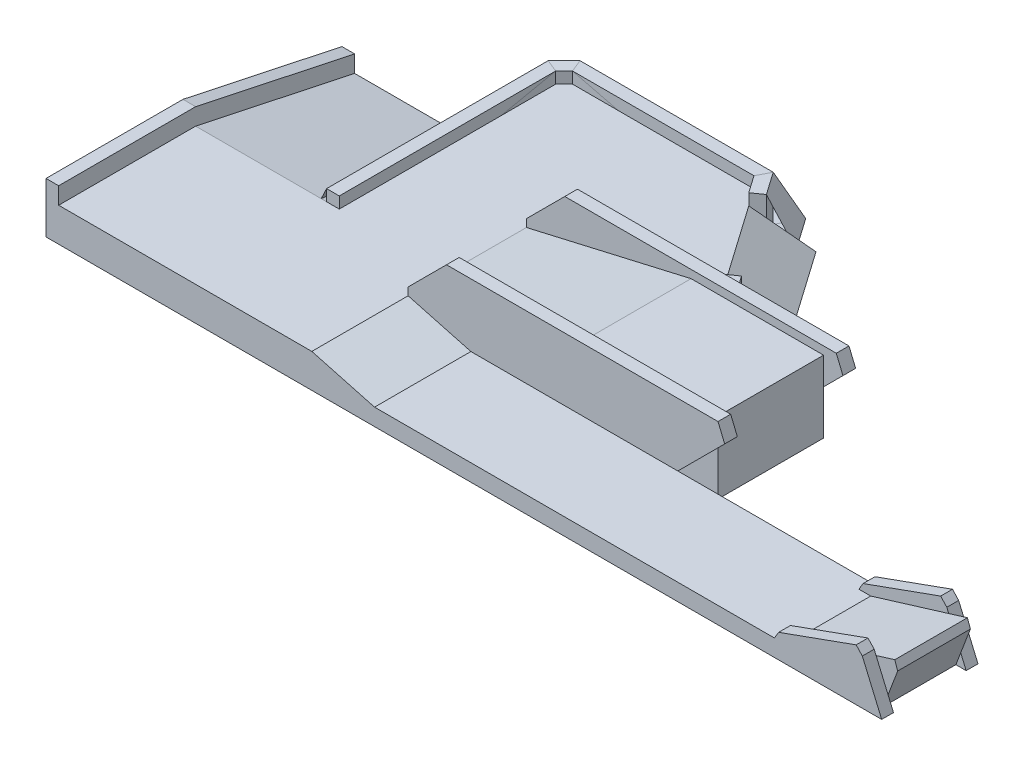
SolidWorks part; units mm, degrees
note: The reader was unsure of these and kept them because the rebuilt part matched: shared geometry of "草图13<4>", "草图18<2>", "草图18<3>", "草图19<2>".
ref_plane "前视基准面" through (0, 0, 0) normal (0, 0, 1) x (1, 0, 0)
ref_plane "上视基准面" through (0, 0, 0) normal (0, 1, 0) x (1, 0, 0)
ref_plane "右视基准面" through (0, 0, 0) normal (1, 0, 0) x (0, 0, -1)
sketch "草图1" plane through (0, 0, 0) normal (0, 1, 0) x (1, 0, 0)
  line L1 (-1498, -810.5) -> (1498, -810.5)
  line L2 (-1498, -810.5) -> (-1498, 810.5)
  line L3 (-1498, 810.5) -> (202, 810.5)
  line L5 (-1498, -810.5) -> (1498, 810.5) construction
  line L6 (-1498, 810.5) -> (1498, -810.5) construction
  line L8 (1498, -810.5) -> (1498, 1879.5)
  line L9 (2449, 3471.5) -> (202, 3471.5)
  line L11 (2449, 3471.5) -> (3563.7304, 1879.5)
  line L12 (3563.7304, 1879.5) -> (1498, 1879.5)
  line L13 (202, 810.5) -> (202, 3471.5)
  point P0 (0, 0)
  point P7 (1666.8134, -901.8373)
  point P8 (1497.9036, 810.5521)
  point P9 (0, 0)
  point P13 (0, 0)
  dimension "D1" = 1592
  dimension "D2" = 1621
  dimension "D3" = 2247
  dimension "D4" = 4282
  dimension "D5" = 2996
  dimension "D6" = 55
  dimension "D7" = 1296
extrude "凸台-拉伸2" add sketch "草图1" along normal blind 400
sketch "草图2" plane through (202, 0, 0) normal (-1, 0, 0) x (0, 0, 1)
  line L0 (-810.5, 0) -> (-2692.3482, 0)
  line L1 (-3471.5, 0) -> (-810.5, 0) construction
  line L2 (-2692.3482, 0) -> (-810.5, 400)
  line L3 (-810.5, 400) -> (-810.5, 0)
  point P5 (0, 0)
  point P8 (0, 0)
  dimension "D2" = 12
extrude "凸台-拉伸21" add sketch "草图2" along normal up to surface (1700 mm away) up to face at (-1498, 200, 0)
sketch "草图8" plane through (0, 0, 0) normal (0, 1, 0) x (1, 0, 0)
  line L1 (1498, 1879.5) -> (5015, 1879.5)
  line L2 (1498, 1879.5) -> (1498, 329.5)
  line L3 (1498, 329.5) -> (5015, 329.5)
  line L4 (5015, 1879.5) -> (5015, 329.5)
  point P5 (0, 0)
  point P6 (0, 0)
  dimension "D1" = 1550
  dimension "D2" = 3517
extrude "凸台-拉伸3" add sketch "草图8" along normal blind 850
sketch "草图9" plane through (0, 0, -329.5) normal (0, 0, 1) x (1, 0, 0)
  line L2 (1498, 850) -> (5015, 850) construction
  line L3 (3447, 850) -> (1498, 400)
  line L4 (1498, 400) -> (1498, 850)
  line L5 (1498, 850) -> (3447, 850)
  dimension "D1" = 1949
extrude "切除-拉伸1" cut sketch "草图9" against normal through all
sketch "草图10" plane through (0, 0, 0) normal (0, 1, 0) x (1, 0, 0)
  line L0 (-1498, -810.5) -> (1498, -810.5) construction
  line L1 (1498, 329.5) -> (7113.18, 329.5)
  line L2 (1498, 329.5) -> (1498, -810.5)
  line L3 (1498, -810.5) -> (7113.18, -810.5)
  line L4 (7113.18, 329.5) -> (7113.18, -810.5)
  dimension "D1" = 5615.18
extrude "凸台-拉伸4" add sketch "草图10" along normal blind 200
sketch "草图11" plane through (0, 0, -329.5) normal (0, 0, 1) x (1, 0, 0)
  line L0 (1498, 400) -> (1498, 200)
  line L1 (1498, 200) -> (2240.68, 200)
  line L2 (5015, 200) -> (1498, 200) construction
  line L3 (2240.68, 200) -> (1498, 400)
  dimension "D1" = 742.68
extrude "凸台-拉伸5" add sketch "草图11" along normal up to surface (1140 mm away) up to face at (2371.06, 200, 810.5)
sketch "草图13" plane through (0, 0, -329.5) normal (0, 0, -1) x (-1, 0, 0)
  line L0 (-7113.18, 0) -> (-5015, 0) construction
  line L1 (-6853.0295, 0) -> (-7023.0932, 283.0844)
  line L2 (-7023.0932, 283.0844) -> (-7940.8821, 613.6353)
  line L3 (-7940.8821, 613.6353) -> (-8013.692, 535.1734)
  line L4 (-8013.692, 535.1734) -> (-8242.6932, 0)
  line L5 (-8242.6932, 0) -> (-6853.0295, 0)
  line L6 (-7113.18, 200) -> (-7113.18, 0) construction
  dimension "D1" = 330.24
  dimension "D2" = 975.5
  dimension "D3" = 107.04
  dimension "D4" = 582.11
  dimension "D5" = 1219.6
  dimension "D6" = 260.1505
  dimension "D7" = 113.053
  dimension "D8" = 66.834
extrude "凸台-拉伸6" add sketch "草图13<4>" against normal blind 140
sketch "草图13<4>" plane through (0, 0, -329.5) normal (0, 0, -1) x (-1, 0, 0) same geometry as "草图13"
sketch "草图15" plane through (0, 0, -189.5) normal (0, 0, 1) x (1, 0, 0)
  line L0 (7113.18, 0) -> (7113.18, 200)
  line L1 (7113.18, 0) -> (7113.18, 200) construction
  line L2 (7113.18, 200) -> (8257.9823, 550)
  line L3 (8257.9823, 550) -> (8292.2785, 451.14)
  line L4 (8292.2785, 451.14) -> (8120.8295, 0)
  line L5 (8242.6932, 0) -> (7113.18, 0) construction
  line L6 (8120.8295, 0) -> (7113.18, 0)
  line L8 (2240.68, 200) -> (7113.18, 200) construction
  point P2 (0, 0)
  point P5 (0, 0)
  point P11 (0, 0)
  point P12 (0, 0)
  dimension "D1" = 104.64
  dimension "D2" = 482.62
  dimension "D3" = 1197.11
  dimension "D4" = 550
  dimension "D5" = 451.14
sketch "草图16" plane through (-1498, 0, 0) normal (-1, 0, 0) x (0, 0, 1)
  line L0 (-810.5, 600) -> (-2692.3482, 200)
  line L2 (810.5, 0) -> (810.5, 600)
  line L3 (810.5, 600) -> (-810.5, 600)
  line L6 (-2692.3482, 200) -> (-2692.3482, 0)
  line L7 (-3471.5, 0) -> (-2692.3482, 0) construction
  line L9 (-2692.3482, 0) -> (810.5, 0)
  line L10 (-3471.5, 0) -> (-2692.3482, 0) construction
  point P3 (0, 0)
  point P5 (-2825.2418, 0)
  dimension "D1" = 600
  dimension "D2" = 200
  dimension "D3" = 1923.89
extrude "凸台-拉伸10" add sketch "草图16" along normal blind 150
sketch "草图17" plane through (0, 0, 0) normal (0, 1, 0) x (1, 0, 0)
  line L1 (202, 810.5) -> (52, 810.5)
  line L9 (3563.7304, 1879.5) -> (3746.8466, 1879.5)
  line L10 (5015, 1879.5) -> (3447, 1879.5) construction
  line L15 (202, 810.5) -> (202, 3371.5)
  line L16 (202, 3471.5) -> (202, 810.5) construction
  line L17 (202, 3371.5) -> (302, 3471.5)
  line L18 (2449, 3471.5) -> (202, 3471.5) construction
  line L19 (302, 3471.5) -> (2449, 3471.5)
  line L20 (2449, 3471.5) -> (3563.7304, 1879.5)
  line L21 (3746.8466, 1879.5) -> (2527.0851, 3621.5)
  line L22 (2527.0851, 3621.5) -> (239.868, 3621.5)
  line L23 (239.868, 3621.5) -> (52, 3433.632)
  line L24 (52, 3433.632) -> (52, 810.5)
  point P1 (0, 0)
  point P18 (0, 0)
  point P20 (0, 0)
  point P22 (0, 0)
  point P23 (0, 0)
  point P24 (0, 0)
  dimension "D1" = 150
  dimension "D2" = 150
  dimension "D3" = 150
  dimension "D4" = 150
  dimension "D5" = 100
  dimension "D6" = 100
extrude "凸台-拉伸11" add sketch "草图17" along normal blind 535 from surface at 0 starting at face at (3258.8059, 0, -1399.6957)
sketch "草图18" plane through (0, 0, -1879.5) normal (0, 0, -1) x (-1, 0, 0)
  line L0 (-4489.876, 0) -> (-5244.44, 754.5857)
  line L1 (-5244.44, 754.5857) -> (-5165.5494, 945)
  line L2 (-5165.5494, 945) -> (-1952.1694, 945)
  line L3 (-1952.1694, 945) -> (-1498, 490.82)
  line L4 (-1498, 490.82) -> (-1498, 0)
  line L6 (-1498, 0) -> (-4489.876, 0)
  line L8 (-5015, 0) -> (-3746.8466, 0) construction
  dimension "D1" = 3213.38
  dimension "D2" = 190.4143
  dimension "D3" = 754.5857
  dimension "D4" = 754.564
  dimension "D5" = 112.496
  dimension "D6" = 642.3
  dimension "D7" = 154.331
extrude "切除-拉伸8" cut sketch "草图18<2>" along normal blind 150 from surface at -1550 starting at face at (3443.136, 500, -329.5)
sketch "草图18<2>" plane through (0, 0, -1879.5) normal (0, 0, -1) x (-1, 0, 0) same geometry as "草图18"
extrude "凸台-拉伸12" add sketch "草图18<3>" against normal blind 150
sketch "草图18<3>" plane through (0, 0, -1879.5) normal (0, 0, -1) x (-1, 0, 0) same geometry as "草图18"
extrude "凸台-拉伸13" add sketch "草图18" against normal blind 150 from surface at -1400 starting at face at (3493.8127, 437.5232, -479.5)
sketch "草图19" plane through (0, 0, -1879.5) normal (0, 0, -1) x (-1, 0, 0)
  line L0 (-5015, 525.1391) -> (-4489.876, 0)
  line L1 (-5015, 0) -> (-3746.8466, 0) construction
  line L2 (-4489.876, 0) -> (-5015, 0)
  line L3 (-5015, 0) -> (-5015, 525.1391)
  line L4 (-5244.44, 754.5857) -> (-5015, 525.1391) construction
extrude "切除-拉伸9" cut sketch "草图19" against normal blind 150
extrude "切除-拉伸10" cut sketch "草图19<2>" along normal blind 150 from surface at -1550 starting at face at (3453.6048, 557.5681, -329.5)
sketch "草图19<2>" plane through (0, 0, -1879.5) normal (0, 0, -1) x (-1, 0, 0) same geometry as "草图19"
sketch "草图20" plane through (0, 535, 0) normal (0, 1, 0) x (1, 0, 0)
  line L0 (2592.3941, 3266.712) -> (3165.8005, 3668.2155)
  line L1 (3563.7304, 1879.5) -> (2449, 3471.5) construction
  line L2 (3165.8005, 3668.2155) -> (3854.0923, 2685.233)
  line L3 (3854.0923, 2685.233) -> (3280.6858, 2283.7295)
  line L4 (3280.6858, 2283.7295) -> (2592.3941, 3266.712)
  dimension "D1" = 1200
  dimension "D2" = 250
  dimension "D3" = 700
extrude "切除-拉伸11" cut sketch "草图20" against normal through all
sketch "草图21" plane through (6.3107, 0, 9.0126) normal (-0.5736, 0, -0.8192) x (-0.8192, 0, 0.5736)
  line L0 (-3997.274, 400) -> (-3997.274, 0)
  line L2 (-3997.274, 0) -> (-4568.5332, 0)
  line L4 (-4568.5332, 0) -> (-3997.274, 400)
  line L5 (-3997.274, 400) -> (-3997.274, 535) construction
  dimension "D1" = 35
extrude "凸台-拉伸14" add sketch "草图21" along normal up to surface (1200 mm away) up to face at (2641.5432, 294, -3301.1266)
extrude "凸台-拉伸18" add sketch "草图15" along normal blind 860
extrude "凸台-拉伸20" add sketch "草图13" against normal blind 140 from surface at -1000 starting at face at (7779.4901, 240.228, 670.5)
sketch "草图35" plane through (0, 0, -810.5) normal (0, 0, 1) x (1, 0, 0)
  line L0 (52, 535) -> (-201, 0)
  line L1 (-1648, 0) -> (8242.6932, 0) construction
  line L2 (-201, 0) -> (202, 0)
  line L4 (-1498, 400) -> (-1498, 600) construction
  line L5 (52, 535) -> (202, 535)
  line L6 (202, 535) -> (202, 0)
  point P9 (52, 0)
  point P13 (0, 0)
  point P14 (190.311, 0)
  dimension "D1" = 1297
sketch "草图37" plane through (0, 400, 0) normal (0, 1, 0) x (1, 0, 0)
  line L0 (202, 810.5) -> (202, 3371.5)
  line L1 (-201, 810.5) -> (202, 810.5) construction
  line L3 (202, 3371.5) -> (302, 3471.5)
  line L4 (302, 3471.5) -> (2449, 3471.5)
  line L8 (2449, 3471.5) -> (2592.3941, 3266.712)
surface "曲面-扫描1"
